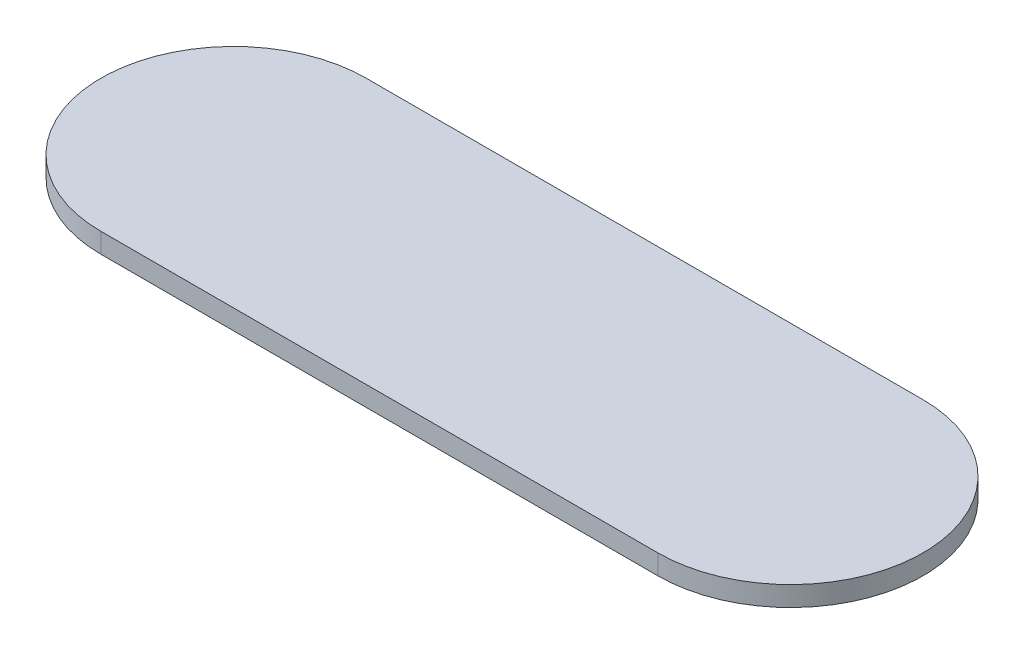
SolidWorks part; units mm, degrees
ref_plane "Front Plane" through (0, 0, 0) normal (0, 0, 1) x (1, 0, 0)
ref_plane "Top Plane" through (0, 0, 0) normal (0, 1, 0) x (1, 0, 0)
ref_plane "Right Plane" through (0, 0, 0) normal (1, 0, 0) x (0, 0, -1)
sketch "Sketch2" plane through (0, 0, 0) normal (0, 1, 0) x (1, 0, 0)
  line L0 (42, 0) -> (-42, 0) construction
  line L1 (42, 20) -> (-42, 20)
  line L2 (42, -20) -> (-42, -20)
  arc A0 (42, 20) -> (42, -20) centre (42, 0) cw
  arc A1 (-42, 20) -> (-42, -20) centre (-42, 0) ccw
  point P4 (0, 0)
  dimension "D1" = 84
  dimension "D2" = 20
  dimension "D3" = 20
extrude "Boss-Extrude1" add sketch "Sketch2" along normal blind 3
